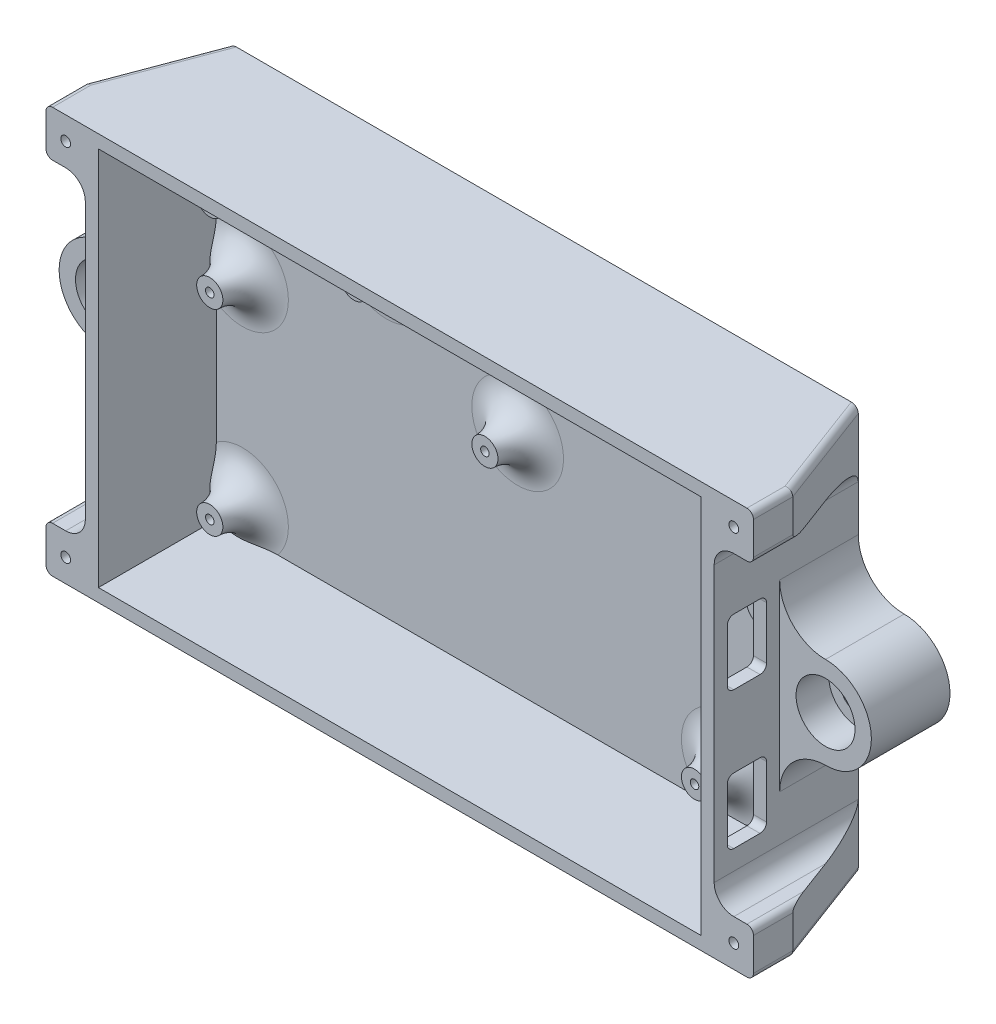
SolidWorks part; units mm, degrees
ref_plane "Спереди" through (0, 0, 0) normal (0, 0, 1) x (1, 0, 0)
ref_plane "Сверху" through (0, 0, 0) normal (0, 1, 0) x (1, 0, 0)
ref_plane "Справа" through (0, 0, 0) normal (1, 0, 0) x (0, 0, -1)
sketch "Эскиз2" plane through (0, 0, 0) normal (0, 0, 1) x (1, 0, 0)
  line L0 (-1000, 0) -> (49000, 0) construction
  line L1 (-48, -31) -> (48, -31)
  line L2 (-48, -31) -> (-48, 31)
  line L3 (-48, 31) -> (48, 31)
  line L4 (48, -31) -> (48, 31)
  line L5 (-48, -31) -> (48, 31) construction
  line L6 (-48, 31) -> (48, -31) construction
  line L7 (0, -1000) -> (0, 49000) construction
  circle A0 centre (-55, 0) radius 2.75
  circle A1 centre (55, 0) radius 2.75
  circle A2 centre (-55, 0) radius 7
  circle A3 centre (55, 0) radius 7
  arc A4 (-55, 7) -> (-48, 14) centre (-55, 14) ccw
  arc A5 (-55, -7) -> (-48, -14) centre (-55, -14) cw
  arc A6 (55, -7) -> (48, -14) centre (55, -14) ccw
  arc A7 (55, 7) -> (48, 14) centre (55, 14) cw
  point P0 (0, 0)
  dimension "D3" = 5.5
  dimension "D1" = 62
  dimension "D2" = 96
  dimension "D4" = 110
extrude "Бобышка-Вытянуть1" add sketch "Эскиз2" along normal blind 4 contours L1 L4 L3 L2 | A4 A2 L2 | A2 A5 L2 | A2 A0 | A3 A7 L4 | A6 A3 L4 | A3 A1 region at (0, 0, 0) region at (-49.5636, -7, 0) region at (49.5636, -7, 0) region at (-49.5636, 7, 0) region at (-50.1903, -4.8097, 0) region at (49.5636, 7, 0) region at (50.1903, 4.8097, 0)
sketch "Эскиз3" plane through (0, 0, 4) normal (0, 0, 1) x (1, 0, 0)
  line L1 (-48, -31) -> (48, -31)
  line L2 (-48, -31) -> (-48, 31)
  line L3 (-48, 31) -> (48, 31)
  line L4 (48, -31) -> (48, 31)
  line L5 (-48, -31) -> (48, 31) construction
  line L6 (-48, -14) -> (-48, -31)
  line L7 (-48, -31) -> (48, -31)
  line L8 (48, -31) -> (48, -14)
  line L9 (48, 14) -> (48, 31)
  line L10 (48, 31) -> (-48, 31)
  line L11 (-48, 31) -> (-48, 14)
  line L12 (-48, -14) -> (-48, -31)
  line L13 (-48, -31) -> (48, -31)
  line L14 (48, -31) -> (48, -14)
  line L15 (48, 14) -> (48, 31)
  line L16 (48, 31) -> (-48, 31)
  line L17 (-48, 31) -> (-48, 14)
  line L18 (-48, 31) -> (48, -31) construction
  line L19 (-46, -29) -> (46, -29)
  line L20 (-46, -29) -> (-46, 29)
  line L21 (-46, 29) -> (46, 29)
  line L22 (46, -29) -> (46, 29)
  line L23 (-46, -29) -> (46, 29) construction
  line L24 (-46, 29) -> (46, -29) construction
  arc A6 (-55, 7) -> (-48, 14) centre (-55, 14) ccw
  arc A7 (-55, 7) -> (-55, -7) centre (-55, 0) ccw
  arc A8 (-48, -14) -> (-55, -7) centre (-55, -14) ccw
  arc A9 (55, -7) -> (48, -14) centre (55, -14) ccw
  arc A10 (55, -7) -> (55, 7) centre (55, 0) ccw
  arc A11 (48, 14) -> (55, 7) centre (55, 14) ccw
  arc A12 (-55, 7) -> (-48, 14) centre (-55, 14) ccw
  arc A13 (-55, 7) -> (-55, -7) centre (-55, 0) ccw
  arc A14 (-48, -14) -> (-55, -7) centre (-55, -14) ccw
  arc A15 (55, -7) -> (48, -14) centre (55, -14) ccw
  arc A16 (55, -7) -> (55, 7) centre (55, 0) ccw
  arc A17 (48, 14) -> (55, 7) centre (55, 14) ccw
  point P0 (0, 0)
  point P3 (0, 0)
  arc M21 (-48, 14) -> (-55, 7) centre (-55, 14) cw
  arc M22 (-55, 7) -> (-55, -7) centre (-55, 0) ccw
  arc M23 (-55, -7) -> (-48, -14) centre (-55, -14) cw
  line M24 (-48, -14) -> (-48, -31)
  line M25 (-48, -31) -> (48, -31)
  line M26 (48, -31) -> (48, -14)
  arc M27 (48, -14) -> (55, -7) centre (55, -14) cw
  arc M28 (55, -7) -> (55, 7) centre (55, 0) ccw
  arc M29 (55, 7) -> (48, 14) centre (55, 14) cw
  line M30 (48, 14) -> (48, 31)
  line M31 (48, 31) -> (-48, 31)
  line M32 (-48, 31) -> (-48, 14)
  circle M33 centre (-55, 0) radius 2.75
  circle M34 centre (55, 0) radius 2.75
  dimension "D2" = 2
  dimension "D3" = 2
  dimension "D1" = 0
extrude "Бобышка-Вытянуть2" add sketch "Эскиз3" along normal blind 18 contours L2 M23 M21 M22 M33 | L4 L2 L22 L19 L20 L21 M26 M30 M31 M32 M24 M25 | L4 M27 M28 M29 M34 region at (-46.8572, -22.5, 4) region at (-49.8289, -8.8289, 4) region at (48.313, 0, 4)
sketch "Эскиз4" plane through (0, 0, 4) normal (0, 0, 1) x (1, 0, 0)
  line L0 (-42, 5.5) -> (-42, -24.5) construction
  line L1 (-45, -27.5) -> (45, -27.5)
  line L2 (-45, -27.5) -> (-45, 27.5)
  line L3 (-45, 27.5) -> (45, 27.5)
  line L4 (46, -29) -> (46, 29)
  line L5 (46, 29) -> (-46, 29)
  line L6 (-46, 29) -> (-46, -29)
  line L7 (-46, -29) -> (46, -29)
  line L8 (46, -29) -> (46, 29)
  line L9 (46, 29) -> (-46, 29)
  line L10 (-46, 29) -> (-46, -29)
  line L11 (-46, -29) -> (46, -29)
  line L12 (45, -27.5) -> (45, 27.5)
  line L13 (-45, -27.5) -> (45, 27.5) construction
  line L14 (-45, 27.5) -> (45, -27.5) construction
  line L15 (-1042, 5.5) -> (48958, 5.5) construction
  line L16 (-1042, -24.5) -> (48958, -24.5) construction
  line L17 (-1042, 17.5) -> (48958, 17.5) construction
  line L18 (-42, 17.5) -> (-42, 5.5) construction
  line L19 (-48, 14) -> (-48, 31) construction
  line L20 (-48, 31) -> (48, 31) construction
  circle A0 centre (-42, -24.5) radius 0.65
  circle A1 centre (-42, 5.5) radius 0.65
  circle A2 centre (0, 5.5) radius 0.65
  circle A3 centre (42, 5.5) radius 0.65
  circle A4 centre (32, -22.5) radius 0.65
  circle A5 centre (-42, 5.5) radius 2
  circle A6 centre (-42, -24.5) radius 2
  circle A7 centre (0, 5.5) radius 2
  circle A8 centre (42, 5.5) radius 2
  circle A9 centre (32, -22.5) radius 2
  circle A10 centre (42, 17.5) radius 0.65
  circle A11 centre (42, 17.5) radius 2
  circle A12 centre (-42, 17.5) radius 0.65
  circle A13 centre (-42, 17.5) radius 2
  circle A14 centre (-20, 17.5) radius 0.65
  circle A15 centre (-20, 17.5) radius 2
  point P2 (0, 0)
  dimension "D10" = 1.3
  dimension "D12" = 4
  dimension "D14" = 65
  dimension "D2" = 90
  dimension "D3" = 55
  dimension "D4" = 3
  dimension "D5" = 30
  dimension "D6" = 3
  dimension "D7" = 42
  dimension "D8" = 13
  dimension "D9" = 5
  dimension "D11" = 42
  dimension "D13" = 10
  dimension "D1" = 0
extrude "Бобышка-Вытянуть3" add sketch "Эскиз4" along normal blind 5 contours A5 A1 | A7 A2 | A8 A3 | A9 A4 | A6 A0 | A15 | A13 | A11 | A12 | A14 | A10 region at (-43.9434, 5.5, 4) region at (-43.9434, -24.5, 4) region at (-1.9434, 5.5, 4) region at (40.0566, 5.5, 4) region at (30.0566, -22.5, 4)
fillet "Скругление1" radius 5 9 edges at (0, 29, 4) (34, -22.5, 4) (44, 5.5, 4) (44, 17.5, 4) (2, 5.5, 4) (-18, 17.5, 4) (-40, -24.5, 4) (-40, 5.5, 4) (-40, 17.5, 4)
sketch "Эскиз6" plane through (0, 0, 22) normal (0, 0, 1) x (1, 0, 0)
  circle A0 centre (-55, 0) radius 4.5
  circle A1 centre (55, 0) radius 4.5
  dimension "D1" = 9
extrude "Вырез-Вытянуть1" cut sketch "Эскиз6" against normal blind 15
sketch "Эскиз7" plane through (0, 31, 0) normal (0, 1, 0) x (1, 0, 0)
  line L0 (-54, -16) -> (-48, 0)
  line L1 (-48, -22) -> (-54, -22)
  line L2 (-48, -22) -> (-48, -16)
  line L3 (-48, -16) -> (-54, -16)
  line L4 (48, 0) -> (-48, 0)
  line L5 (-48, 0) -> (-48, -22)
  line L6 (-48, -22) -> (48, -22)
  line L7 (48, -22) -> (48, 0)
  line L8 (48, 0) -> (-48, 0)
  line L9 (-48, 0) -> (-48, -22)
  line L10 (-48, -22) -> (48, -22)
  line L11 (48, -22) -> (48, 0)
  line L12 (-54, -22) -> (-54, -16)
  line L13 (0, -1000) -> (0, 49000) construction
  line L14 (54, -16) -> (48, 0)
  line L15 (48, -22) -> (48, -16)
  line L16 (48, -22) -> (54, -22)
  line L17 (54, -22) -> (54, -16)
  line L18 (48, -16) -> (54, -16)
  line M8 (-48, 0) -> (-48, -22)
  line M10 (48, -22) -> (48, 0)
  dimension "D2" = 6
  dimension "D3" = 6
  dimension "D1" = 0
extrude "Бобышка-Вытянуть4" add sketch "Эскиз7" against normal blind 7 contours L12 L1 L3 M8 | L3 L0 M8 | L18 L16 L17 M10 | L11 L18 L14 region at (-50, 31, 10.6667) region at (-51, 31, 19) region at (50, 31, 10.6667) region at (51, 31, 19)
mirror "Зеркальное отражение1" about plane through (0, 0, 0) normal (0, 1, 0) of "Бобышка-Вытянуть4"
sketch "Эскиз8" plane through (0, 0, 22) normal (0, 0, 1) x (1, 0, 0)
  line L0 (-1054, 27.5) -> (48946, 27.5) construction
  line L1 (-51, -976) -> (-51, 49024) construction
  line L2 (0, -1000) -> (0, 49000) construction
  line L3 (-1000, 0) -> (49000, 0) construction
  line L14 (-48, -14) -> (-48, -24)
  line L15 (-48, -24) -> (-54, -24)
  line L16 (-54, -24) -> (-54, -31)
  line L17 (-54, -31) -> (54, -31)
  line L18 (54, -31) -> (54, -24)
  line L19 (54, -24) -> (48, -24)
  line L20 (48, -24) -> (48, -14)
  line L21 (48, 14) -> (48, 24)
  line L22 (48, 24) -> (54, 24)
  line L23 (54, 24) -> (54, 31)
  line L24 (54, 31) -> (-54, 31)
  line L25 (-54, 31) -> (-54, 24)
  line L26 (-54, 24) -> (-48, 24)
  line L27 (-48, 24) -> (-48, 14)
  line L28 (-48, -14) -> (-48, -24)
  line L29 (-48, -24) -> (-54, -24)
  line L30 (-54, -24) -> (-54, -31)
  line L31 (-54, -31) -> (54, -31)
  line L32 (54, -31) -> (54, -24)
  line L33 (54, -24) -> (48, -24)
  line L34 (48, -24) -> (48, -14)
  line L35 (48, 14) -> (48, 24)
  line L36 (48, 24) -> (54, 24)
  line L37 (54, 24) -> (54, 31)
  line L38 (54, 31) -> (-54, 31)
  line L39 (-54, 31) -> (-54, 24)
  line L40 (-54, 24) -> (-48, 24)
  line L41 (-48, 24) -> (-48, 14)
  circle A0 centre (-51, 27.5) radius 0.75
  circle A1 centre (51, 27.5) radius 0.75
  circle A2 centre (51, -27.5) radius 0.75
  circle A3 centre (-51, -27.5) radius 0.75
  arc A6 (-48, -14) -> (-55, -7) centre (-55, -14) ccw
  arc A7 (55, -7) -> (48, -14) centre (55, -14) ccw
  arc A8 (55, -7) -> (55, 7) centre (55, 0) ccw
  arc A9 (48, 14) -> (55, 7) centre (55, 14) ccw
  arc A10 (-55, 7) -> (-48, 14) centre (-55, 14) ccw
  arc A11 (-55, 7) -> (-55, -7) centre (-55, 0) ccw
  arc A12 (-48, -14) -> (-55, -7) centre (-55, -14) ccw
  arc A13 (55, -7) -> (48, -14) centre (55, -14) ccw
  arc A14 (55, -7) -> (55, 7) centre (55, 0) ccw
  arc A15 (48, 14) -> (55, 7) centre (55, 14) ccw
  arc A16 (-55, 7) -> (-48, 14) centre (-55, 14) ccw
  arc A17 (-55, 7) -> (-55, -7) centre (-55, 0) ccw
  point P21 (-54, 27.5)
  point P30 (-51, 24)
  dimension "D2" = 1.5
  dimension "D1" = 0
extrude "Вырез-Вытянуть2" cut sketch "Эскиз8" against normal blind 7 flip side to cut
sketch "Эскиз9" plane through (48, 0, 0) normal (1, 0, 0) x (0, 0, -1)
  line L1 (-4, 6.15) -> (-4, 4.85)
  line L2 (-4, 6.15) -> (-4, 4.85)
  line L3 (-4, -23.85) -> (-4, -25.15)
  line L4 (-4, -23.85) -> (-4, -25.15)
  line L5 (-16, 31) -> (0, 31) construction
  line L6 (-20, 3) -> (-14, 3)
  line L7 (-20, 3) -> (-20, 13)
  line L8 (-20, 13) -> (-14, 13)
  line L9 (-14, 3) -> (-14, 13)
  line L10 (-20, -18) -> (-14, -18)
  line L11 (-20, -18) -> (-20, -8)
  line L12 (-20, -8) -> (-14, -8)
  line L13 (-14, -18) -> (-14, -8)
  line L14 (-16, -31) -> (0, -31) construction
  line L15 (0, 14) -> (0, 24) construction
  dimension "D3" = 6
  dimension "D4" = 10
  dimension "D5" = 18
  dimension "D6" = 13
  dimension "D7" = 14
  dimension "D1" = 0
  dimension "D2" = 0
extrude "Вырез-Вытянуть3" cut sketch "Эскиз9" against normal mid plane 30 contours L10 L13 L12 L11 | L7 L8 L9 L6 region at (48, -13, 17)
sketch "Эскиз10" plane through (0, 0, 22) normal (0, 0, 1) x (1, 0, 0)
  line L0 (48, 14) -> (48, -14)
  line L1 (-48, 14) -> (-48, -14)
  line L14 (-48, -14) -> (-48, -24)
  line L15 (-48, -24) -> (-54, -24)
  line L16 (-54, -24) -> (-54, -31)
  line L17 (-54, -31) -> (54, -31)
  line L18 (54, -31) -> (54, -24)
  line L19 (54, -24) -> (48, -24)
  line L20 (48, -24) -> (48, -14)
  line L21 (48, 14) -> (48, 24)
  line L22 (48, 24) -> (54, 24)
  line L23 (54, 24) -> (54, 31)
  line L24 (54, 31) -> (-54, 31)
  line L25 (-54, 31) -> (-54, 24)
  line L26 (-54, 24) -> (-48, 24)
  line L27 (-48, 24) -> (-48, 14)
  line L28 (-48, -14) -> (-48, -24)
  line L29 (-48, -24) -> (-54, -24)
  line L30 (-54, -24) -> (-54, -31)
  line L31 (-54, -31) -> (54, -31)
  line L32 (54, -31) -> (54, -24)
  line L33 (54, -24) -> (48, -24)
  line L34 (48, -24) -> (48, -14)
  line L35 (48, 14) -> (48, 24)
  line L36 (48, 24) -> (54, 24)
  line L37 (54, 24) -> (54, 31)
  line L38 (54, 31) -> (-54, 31)
  line L39 (-54, 31) -> (-54, 24)
  line L40 (-54, 24) -> (-48, 24)
  line L41 (-48, 24) -> (-48, 14)
  arc A6 (-48, -14) -> (-55, -7) centre (-55, -14) ccw
  arc A7 (55, -7) -> (48, -14) centre (55, -14) ccw
  arc A8 (55, -7) -> (55, 7) centre (55, 0) ccw
  arc A9 (48, 14) -> (55, 7) centre (55, 14) ccw
  arc A10 (-55, 7) -> (-48, 14) centre (-55, 14) ccw
  arc A11 (-55, 7) -> (-55, -7) centre (-55, 0) ccw
  arc A12 (-48, -14) -> (-55, -7) centre (-55, -14) ccw
  arc A13 (55, -7) -> (48, -14) centre (55, -14) ccw
  arc A14 (55, -7) -> (55, 7) centre (55, 0) ccw
  arc A15 (48, 14) -> (55, 7) centre (55, 14) ccw
  arc A16 (-55, 7) -> (-48, 14) centre (-55, 14) ccw
  arc A17 (-55, 7) -> (-55, -7) centre (-55, 0) ccw
  circle M25 centre (-55, 0) radius 4.5
  circle M26 centre (55, 0) radius 4.5
  arc M27 (-55, -7) -> (-48, -14) centre (-55, -14) cw
  arc M35 (48, -14) -> (55, -7) centre (55, -14) cw
  arc M36 (55, -7) -> (55, 7) centre (55, 0) ccw
  arc M37 (55, 7) -> (48, 14) centre (55, 14) cw
  arc M45 (-48, 14) -> (-55, 7) centre (-55, 14) cw
  arc M46 (-55, 7) -> (-55, -7) centre (-55, 0) ccw
  dimension "D1" = 0
extrude "Вырез-Вытянуть4" cut sketch "Эскиз10" against normal blind 10 contours L0 M37 M35 M36 M26 | L1 M45 M46 M27 M25 region at (49.8289, 8.8289, 22) region at (-48.313, 0, 22)
fillet "Скругление3" radius 1 4 edges at (47, 13, 20) (47, 13, 14) (47, 3, 20) (47, 3, 14)
fillet "Скругление4" radius 1 4 edges at (47, -18, 20) (47, -8, 20) (47, -8, 14) (47, -18, 14)
fillet "Скругление5" radius 3 4 edges at (-48, -24, 11) (-48, 24, 11) (48, 24, 11) (48, -24, 11)
fillet "Скругление6" radius 1 3 edges at (-51, 31, 8) (-54, 31, 19) (-54, 24, 19)
fillet "Скругление8" radius 1 9 edges at (54, 24, 19) (51, 31, 8) (54, 31, 19) (54, -24, 19) (51, -31, 8) (54, -31, 19) (-54, -31, 19) (-51, -31, 8) (-54, -24, 19)
